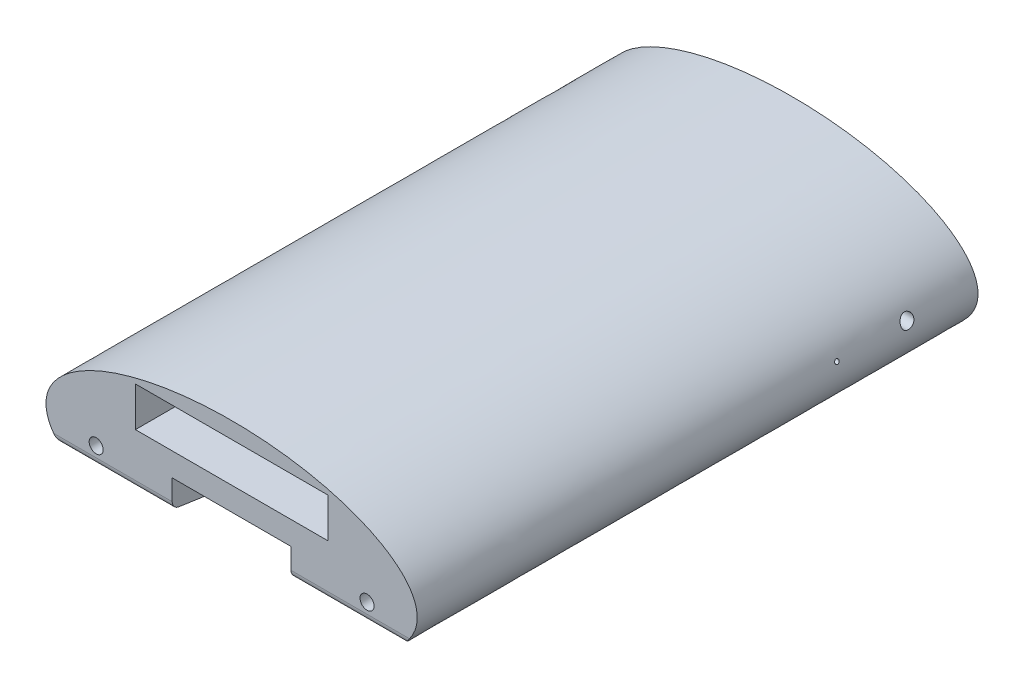
SolidWorks part; units mm, degrees
material "UoS Blue Foam"
ref_plane "Front Plane" through (0, 0, 0) normal (0, 0, 1) x (1, 0, 0)
ref_plane "Top Plane" through (0, 0, 0) normal (0, 1, 0) x (1, 0, 0)
ref_plane "Right Plane" through (0, 0, 0) normal (1, 0, 0) x (0, 0, -1)
sketch "Sketch1" plane through (0, 0, 0) normal (0, 0, 1) x (1, 0, 0)
  line L0 (0, -38.5) -> (0, 38.5) construction
  line L1 (-123.4, 119.3) -> (123.4, 119.3)
  line L2 (-123.4, 119.3) -> (-123.4, 68.5)
  line L3 (-123.4, 68.5) -> (123.4, 68.5)
  line L4 (123.4, 119.3) -> (123.4, 68.5)
  line L5 (-76.2, 38.5) -> (76.2, 38.5)
  line L6 (-76.2, 38.5) -> (-76.2, -38.5)
  line L7 (-76.2, -38.5) -> (76.2, -38.5)
  line L8 (76.2, 38.5) -> (76.2, -38.5)
  line L9 (0, 119.3) -> (0, 68.5) construction
  line L10 (-76.2, 0) -> (76.2, 0) construction
  line L11 (238.1768, 40.4) -> (-238.1768, 40.4) construction
  circle A2 centre (173.785, 25.4) radius 9
  circle A3 centre (-173.785, 25.4) radius 9
  ellipse E0 centre (0, 40.4) end of major axis (238.1768, 40.4) minor radius 100
  point P16 (0, 0)
  dimension "D1" = 18
  dimension "PAX_Height" = 50.8
  dimension "PAX_Width" = 246.8
  dimension "Cargo_Height" = 77
  dimension "Cargo_Width" = 152.4
  dimension "PAX_Cargo_Spacing_Y" = 30
  dimension "Ellipse_Semi_Minor" = 100
  dimension "Ellipse_Semi_Major" = 238.1768
  dimension "Ellipse_Centre_Y" = 78.9
  dimension "D2" = 173.785
  dimension "D3" = 15
extrude "Boss-Extrude1" add sketch "Sketch1" along normal blind 719.55
sketch "Sketch3" plane through (0, 0, 0) normal (1, 0, 0) x (0, 0, -1)
  line L0 (-201.1748, -72) -> (-731.1748, 5)
  dimension "D1" = 530
  dimension "D2" = 77
extrude "Cut-Extrude1" cut sketch "Sketch3" against normal through all and the other way through all
fillet "Fillet1" radius 10 2 edges at (148.6947, 3.3111, 719.55) (-148.6947, 3.3111, 719.55)
sketch "Sketch4" plane through (0, -38.5, 0) normal (0, 1, 0) x (1, 0, 0)
  line L0 (-76.2, -431.7593) -> (-76.2, 0) construction
  line L1 (76.2, -431.7593) -> (-76.2, -431.7593)
  line L2 (76.2, -431.7593) -> (76.2, -154)
  line L3 (76.2, -154) -> (-76.2, -154)
  line L4 (-76.2, -431.7593) -> (-76.2, -154)
  line L5 (-76.2, 0) -> (76.2, 0) construction
  dimension "D1" = 154
extrude "Boss-Extrude2" add sketch "Sketch4" along normal up to next
sketch "Sketch5" plane through (0, 0, 0) normal (1, 0, 0) x (0, 0, -1)
  line L1 (-154, 38.5) -> (-154, -38.5) construction
  line L3 (-154, 38.5) -> (0, 38.5) construction
  circle A0 centre (-179, 53.5) radius 2.75
  circle A1 centre (-89, 53.5) radius 8.5
  dimension "D1" = 25
  dimension "D2" = 5.5
  dimension "D4" = 90
  dimension "D5" = 17
  dimension "D3" = 15
extrude "Cut-Extrude2" cut sketch "Sketch5" against normal through all both and the other way through all
equation "\"Ellipse_Centre_Y@Sketch1\" = ( \"Cargo_Height@Sketch1\" + \"PAX_Cargo_Spacing_Y@Sketch1\" + \"PAX_Height@Sketch1\" )  / 2"
equation "\"PAX\"= 52"
equation "\"Cargo\"= 4"
